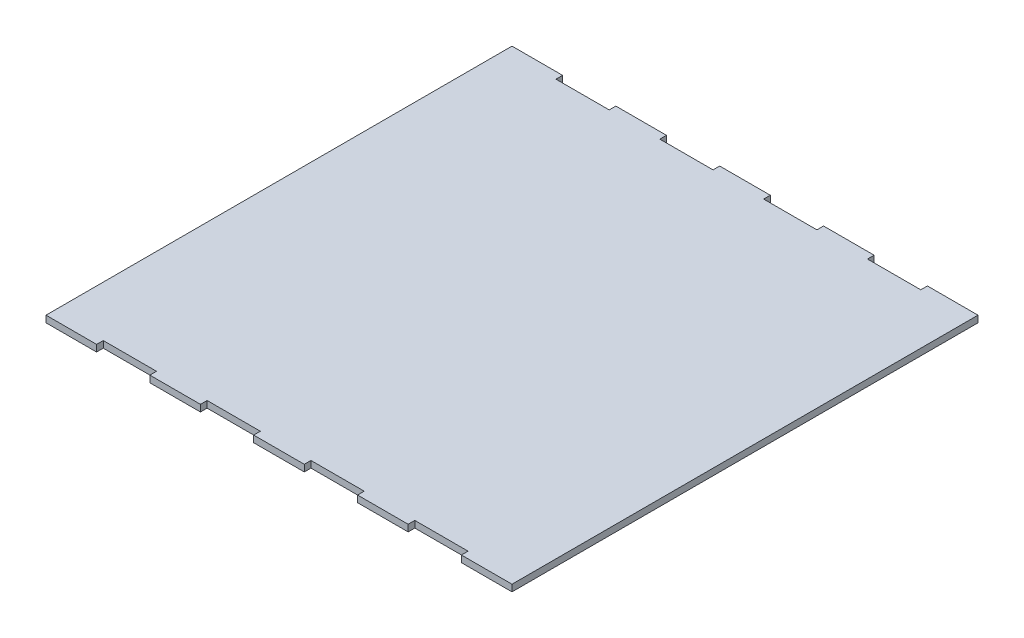
SolidWorks part; units mm, degrees
ref_plane "Front" through (0, 0, 0) normal (0, 0, 1) x (1, 0, 0)
ref_plane "Top" through (0, 0, 0) normal (0, 1, 0) x (1, 0, 0)
ref_plane "Right" through (0, 0, 0) normal (1, 0, 0) x (0, 0, -1)
sketch "Skizze1" plane through (0, 0, 0) normal (0, 1, 0) x (1, 0, 0)
  line L1 (175, 175) -> (-175, 175)
  line L2 (175, 175) -> (175, -175)
  line L3 (175, -175) -> (-175, -175)
  line L4 (-175, 175) -> (-175, -175)
  line L5 (175, 175) -> (-175, -175) construction
  line L6 (175, -175) -> (-175, 175) construction
  point P0 (0, 0)
  dimension "D1" = 350
  dimension "D2" = 350
extrude "Grundplatte" add sketch "Skizze1" along normal blind 5
ref_plane "Ebene1" through (0, 0, 0) normal (0, 0, 1) x (1, 0, 0)
ref_plane "Ebene2" through (0, 0, 0) normal (-1, 0, 0) x (0, 0, 1)
sketch "Skizze2" plane through (0, 5, 0) normal (0, 1, 0) x (1, 0, 0)
  line L0 (-175, 175) -> (-175, -175) construction
  line L5 (0, 175) -> (0, 0) construction
  line L6 (175, 175) -> (-175, 175) construction
  line L7 (137, 170) -> (175, 170) construction
  line L8 (19, 170) -> (-19, 170) construction
  line L13 (-137, 175) -> (-97, 175)
  line L14 (-137, 175) -> (-137, 170)
  line L15 (-137, 170) -> (-97, 170)
  line L16 (-97, 175) -> (-97, 170)
  line L17 (-59, 175) -> (-19, 175)
  line L18 (-59, 175) -> (-59, 170)
  line L19 (-59, 170) -> (-19, 170)
  line L20 (-19, 175) -> (-19, 170)
  line L21 (-59, 170) -> (-97, 170) construction
  line L22 (-137, 170) -> (-175, 170) construction
  line L23 (59, 170) -> (97, 170) construction
  line L24 (19, 175) -> (19, 170)
  line L25 (59, 170) -> (19, 170)
  line L42 (59, 175) -> (59, 170)
  line L43 (59, 175) -> (19, 175)
  line L44 (97, 175) -> (97, 170)
  line L45 (137, 170) -> (97, 170)
  line L46 (137, 175) -> (137, 170)
  line L63 (137, 175) -> (97, 175)
  point P12 (0, 170)
  dimension "D1" = 40
  dimension "D2" = 5
  dimension "D3" = 38
extrude "Schnitt-Linear austragen1" cut sketch "Skizze2" against normal through all
mirror "Spiegeln1" about plane through (0, 0, 0) normal (0, 0, 1) of "Schnitt-Linear austragen1"
ref_axis "Achse1" through (0, 10.2665, 0) along (0, -1, 0)
pattern_circular "Kreismuster1" [suppressed] count 2 over 90 about axis through (0, 10.2665, 0) along (0, -1, 0) of bodies 103
